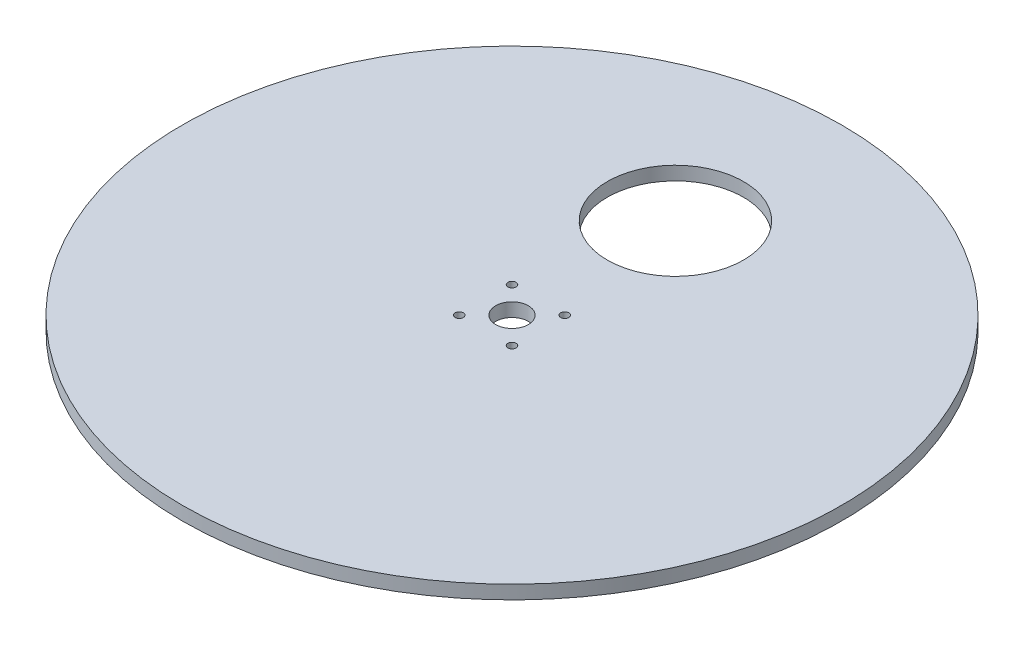
SolidWorks part; units mm, degrees
ref_plane "Front Plane" through (0, 0, 0) normal (0, 0, 1) x (1, 0, 0)
ref_plane "Top Plane" through (0, 0, 0) normal (0, 1, 0) x (1, 0, 0)
ref_plane "Right Plane" through (0, 0, 0) normal (1, 0, 0) x (0, 0, -1)
sketch "Sketch1" plane through (0, 0, 0) normal (0, 1, 0) x (1, 0, 0)
  line L0 (0, 0) -> (0, 169.8963) construction
  circle A0 centre (0, 0) radius 121
  circle A1 centre (0, 0) radius 6
  circle A2 centre (0, 60) radius 25
  circle A3 centre (9.6862, 9.6862) radius 1.5
  circle A4 centre (-9.6862, 9.6862) radius 1.5
  circle A5 centre (-9.6862, -9.6862) radius 1.5
  circle A6 centre (9.6862, -9.6862) radius 1.5
  dimension "D1" = 242
  dimension "D2" = 12
  dimension "D3" = 50
  dimension "D4" = 60
extrude "Boss-Extrude1" add sketch "Sketch1" along normal blind 5
